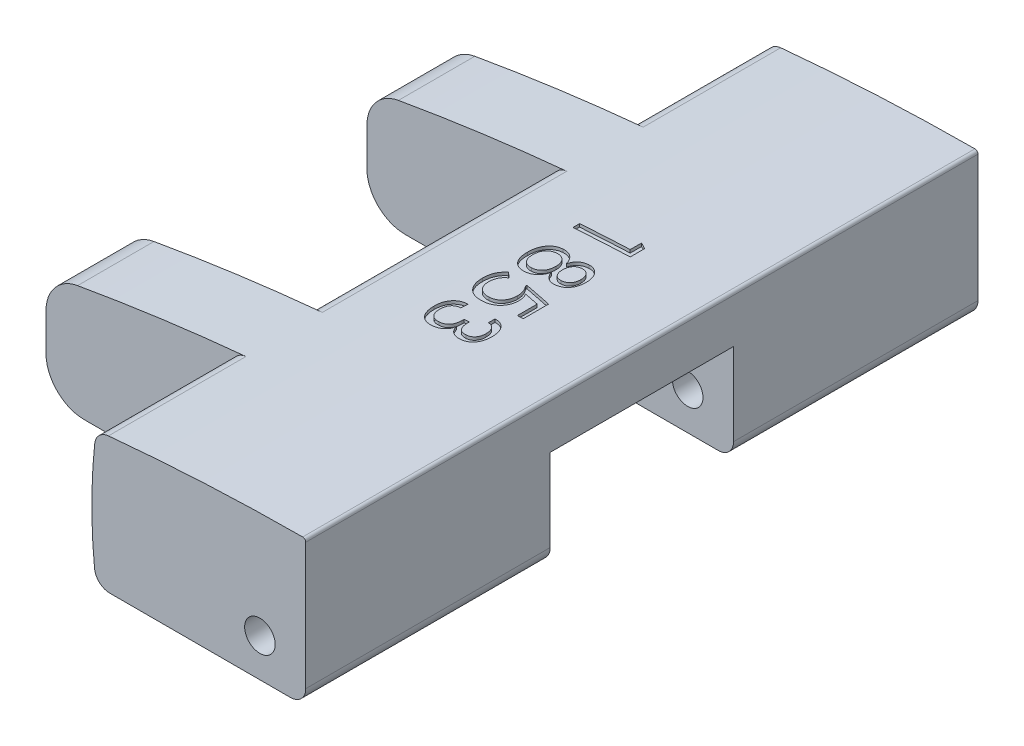
SolidWorks part; units mm, degrees
note: The reader was unsure of these and kept them because the rebuilt part matched: shared geometry of "Sketch3<2>".
ref_plane "Front Plane" through (0, 0, 0) normal (0, 0, 1) x (1, 0, 0)
ref_plane "Top Plane" through (0, 0, 0) normal (0, 1, 0) x (1, 0, 0)
ref_plane "Right Plane" through (0, 0, 0) normal (1, 0, 0) x (0, 0, -1)
sketch "Sketch1" plane through (0, 0, 0) normal (0, 0, 1) x (1, 0, 0)
  line L0 (55, 0) -> (-55, 0) construction
  line L1 (-6.5, 2.75) -> (6.5, 2.75)
  line L2 (-6.5, 2.75) -> (-6.5, -2)
  line L3 (-6.5, -2) -> (6.5, -2)
  line L4 (6.5, 2.75) -> (6.5, -2)
  line L5 (0, -55) -> (0, 55) construction
  dimension "D1" = 4.75
  dimension "D2" = 2
  dimension "D3" = 13
  dimension "D4" = 6.5
extrude "Boss-Extrude1" add sketch "Sketch1" along normal blind 22
sketch "Sketch2" plane through (0, 0, 22) normal (0, 0, 1) x (1, 0, 0)
  line L0 (-6.5, 2.75) -> (-6.5, -2) construction
  line L1 (6.5, 2.75) -> (-6.5, 2.75) construction
  line L2 (-6.5, 1.5) -> (-7.8176, 1.5)
  line L3 (-7.8176, 1.5) -> (-7.8176, 4.1621)
  line L4 (-7.8176, 4.1621) -> (6.8154, 3.9473)
  line L5 (6.8154, 3.9473) -> (6.5, 2.75)
  arc A0 (6.5, 2.75) -> (-6.5, 1.5) centre (6.6707, -67.2498) ccw
  dimension "D2" = 70
  dimension "D1" = 1.25
extrude "Cut-Extrude1" cut sketch "Sketch2" against normal blind 22
sketch "Sketch3" plane through (0, 0, 22) normal (0, 0, 1) x (1, 0, 0)
  line L1 (-8.7194, 4.2963) -> (-0.5, 4.2963)
  line L2 (-8.7194, 4.2963) -> (-8.7194, -4.8901)
  line L3 (-8.7194, -4.8901) -> (-0.5, -4.8901)
  line L5 (-6.5, -2) -> (6.5, -2) construction
  line L6 (-0.3595, 2.3963) -> (-0.5, 4.2963)
  line L7 (-0.3595, -2) -> (-0.5, -4.8901)
  arc A0 (-0.3595, 2.3963) -> (-0.3595, -2) centre (16.7667, 0.1981) ccw
  arc A1 (6.5, 2.75) -> (-6.5, 1.5) centre (6.6707, -67.2498) ccw construction
extrude "Cut-Extrude2" cut sketch "Sketch3" against normal blind 4.5
extrude "Cut-Extrude3" cut sketch "Sketch3<2>" along normal blind 4.5 from offset 22 offset against normal yes
sketch "Sketch3<2>" plane through (0, 0, 22) normal (0, 0, 1) x (1, 0, 0) same geometry as "Sketch3"
fillet "Fillet1" radius 0.5 4 edges at (-0.3595, -2, 19.75) (-0.3595, -2, 2.25) (-0.3595, 2.3963, 19.75) (-0.3595, 2.3963, 2.25)
fillet "Fillet2" radius 0.5 1 edges at (6.5, -2, 11)
fillet "Fillet3" radius 0.1 1 edges at (6.5, 2.75, 11)
sketch "Sketch4" plane through (0, 0, 22) normal (0, 0, 1) x (1, 0, 0)
  line L0 (0.0862, -2) -> (6, -2) construction
  line L1 (6.5, -1.5) -> (6.5, 2.6497) construction
  circle A0 centre (5, -0.75) radius 0.5
  dimension "D3" = 1
  dimension "D1" = 1.25
  dimension "D2" = 1.5
extrude "Cut-Extrude4" cut sketch "Sketch4" against normal blind 24.5
fillet "Fillet4" radius 1.25 2 edges at (-6.5, -2, 11) (-6.5, 1.5, 11)
sketch "Sketch5" plane through (0, 0, 17.5) normal (0, 0, 1) x (1, 0, 0)
  line L0 (7.15, 0) -> (-7.15, 0) construction
  line L1 (0, -2.6123) -> (0, 2.6123) construction
  circle A0 centre (-2, -0.5) radius 0.5
  dimension "D1" = 1
  dimension "D2" = 0.5
  dimension "D3" = 2
extrude "Cut-Extrude5" cut sketch "Sketch5" against normal blind 24.5
sketch "Sketch6" plane through (0, 0, 17.5) normal (0, 0, 1) x (1, 0, 0)
  line L2 (-6.5, 0.4589) -> (-6.5, -0.75)
  line L3 (-5.25, -2) -> (0.0862, -2)
  line L4 (-6.5, 0.4589) -> (-6.5, -0.75)
  line L5 (-5.25, -2) -> (0.0862, -2)
  arc A6 (-6.5, -0.75) -> (-5.25, -2) centre (-5.25, -0.75) ccw
  arc A7 (-0.4112, -1.5506) -> (0.0862, -2) centre (0.0862, -1.5) ccw
  arc A8 (-0.4068, 1.9899) -> (-0.4112, -1.5506) centre (16.7667, 0.1981) ccw
  arc A9 (0.0432, 2.4358) -> (-0.4068, 1.9899) centre (0.0905, 1.938) ccw
  arc A10 (0.0432, 2.4358) -> (-5.4667, 1.6899) centre (6.6707, -67.2498) ccw
  arc A11 (-5.4667, 1.6899) -> (-6.5, 0.4589) centre (-5.25, 0.4589) ccw
  arc A12 (-6.5, -0.75) -> (-5.25, -2) centre (-5.25, -0.75) ccw
  arc A13 (-0.4112, -1.5506) -> (0.0862, -2) centre (0.0862, -1.5) ccw
  arc A14 (-0.4068, 1.9899) -> (-0.4112, -1.5506) centre (16.7667, 0.1981) ccw
  arc A15 (0.0432, 2.4358) -> (-0.4068, 1.9899) centre (0.0905, 1.938) ccw
  arc A16 (0.0432, 2.4358) -> (-5.4667, 1.6899) centre (6.6707, -67.2498) ccw
  arc A17 (-5.4667, 1.6899) -> (-6.5, 0.4589) centre (-5.25, 0.4589) ccw
  dimension "D1" = 0
extrude "Cut-Extrude6" cut sketch "Sketch6" against normal offset from surface (8 mm away) 2.5 from offset 2.5 up to face at (-1.5, -0.5, 4.5) offset against normal yes
sketch "Sketch7" plane through (0, 0, 22) normal (0, 0, 1) x (1, 0, 0)
  line L0 (0, -2.6123) -> (0, 2.6123) construction
  line L1 (6.5, -1.5) -> (6.5, 2.6497) construction
  line L2 (0, -1.9948) -> (-0.1145, -3.67)
  line L3 (-0.1145, -3.67) -> (10.4521, -3.3979)
  line L4 (10.4521, -3.3979) -> (6.5, 1.1981)
  arc A0 (0, -1.9948) -> (6.5, 1.1981) centre (6.3877, -6.7859) cw
extrude "Cut-Extrude7" cut sketch "Sketch7" against normal blind 6 from offset 8 offset against normal yes
sketch "Sketch11" plane through (0, 0, 0) normal (0, 1, 0) x (1, 0, 0)
  line L0 (1.8879, -7.7434) -> (1.8879, -14.351)
sketch "Sketch10" plane through (0, 0, 0) normal (0, 1, 0) x (1, 0, 0)
  text T0 "1853" font "Futura Bk BT" height in points 7
extrude "Cut-Extrude8" cut sketch "Sketch10" against normal offset from surface (7.4102 mm away) 0.1 from offset 10
